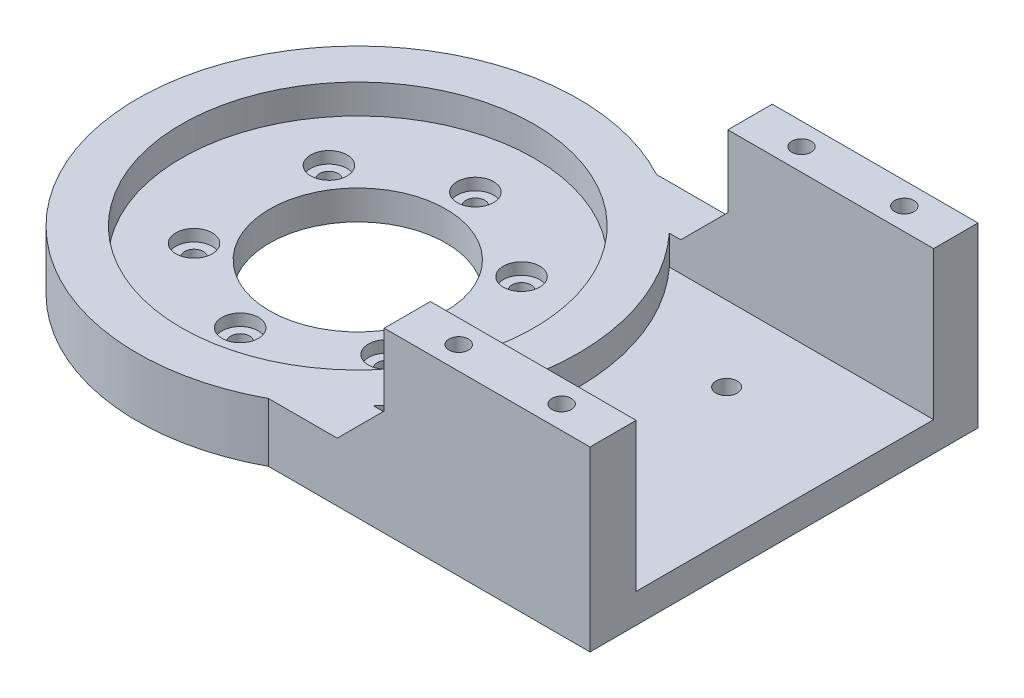
SolidWorks part; units mm, degrees
ref_plane "Front Plane" through (0, 0, 0) normal (0, 0, 1) x (1, 0, 0)
ref_plane "Top Plane" through (0, 0, 0) normal (0, 1, 0) x (1, 0, 0)
ref_plane "Right Plane" through (0, 0, 0) normal (1, 0, 0) x (0, 0, -1)
sketch "Sketch1" plane through (0, 0, 0) normal (0, 1, 0) x (1, 0, 0)
  circle A0 centre (0, 0) radius 15
  circle A1 centre (0, 0) radius 37.5
  dimension "D1" = 30
  dimension "D2" = 75
extrude "Boss-Extrude2" add sketch "Sketch1" along normal blind 5
sketch "Sketch3" plane through (0, 5, 0) normal (0, 1, 0) x (1, 0, 0)
  circle A0 centre (0, 0) radius 30
  circle A1 centre (0, 0) radius 37.5
  dimension "D1" = 60
extrude "Boss-Extrude3" add sketch "Sketch3" along normal blind 5
sketch "Sketch4" plane through (0, 5, 0) normal (0, 1, 0) x (1, 0, 0)
  line L0 (0, 0) -> (0, 20) construction
  line L1 (0, 0) -> (-16.383, 11.4715) construction
  line L2 (0, 0) -> (16.383, 11.4715) construction
  line L3 (0, 0) -> (-7.7431, 0) construction
  circle A0 centre (0, 20) radius 1.6
  circle A1 centre (-16.383, 11.4715) radius 1.6
  circle A2 centre (16.383, 11.4715) radius 1.6
  circle A3 centre (16.383, -11.4715) radius 1.6
  circle A4 centre (0, -20) radius 1.6
  circle A5 centre (-16.383, -11.4715) radius 1.6
  dimension "D2" = 3.2
  dimension "D1" = 20
  dimension "D3" = 55
  dimension "D4" = 20
  dimension "D5" = 55
  dimension "D6" = 20
extrude "Cut-Extrude1" cut sketch "Sketch4" against normal blind 5
sketch "Sketch5" plane through (0, 5, 0) normal (0, 1, 0) x (1, 0, 0)
  line L0 (0, 0) -> (-6.2782, 0) construction
  circle A0 centre (0, 20) radius 3.1
  circle A1 centre (-16.383, 11.4715) radius 3.1
  circle A2 centre (16.383, 11.4715) radius 3.1
  circle A3 centre (16.383, -11.4715) radius 3.1
  circle A4 centre (-16.383, -11.4715) radius 3.1
  circle A5 centre (0, -20) radius 3.1
  dimension "D1" = 6.2
extrude "Cut-Extrude2" cut sketch "Sketch5" against normal blind 2
sketch "Sketch6" plane through (0, 5, 0) normal (0, 1, 0) x (1, 0, 0)
  line L1 (-15, 0) -> (15, 0) construction
  circle A1 centre (0, 0) radius 15 construction
ref_plane "Plane1" through (37.5, 0, 0) normal (1, 0, 0) x (0, 0, -1)
sketch "Sketch8" plane through (37.5, 0, 0) normal (1, 0, 0) x (0, 0, -1)
  line L0 (0, 10) -> (0, 0) construction
  line L1 (37.5, 10) -> (-37.5, 10) construction
  line L2 (0, 5) -> (-25.15, 5) construction
  line L3 (0, 5) -> (25.45, 5) construction
  line L4 (-10.1453, 5) -> (-10.1453, 0) construction
  line L5 (-37.5, 0) -> (37.5, 0) construction
  line L6 (33, 5) -> (-33, 5) construction
  line L7 (33, 10) -> (33, 0)
  line L8 (-33, 0) -> (-33, 10)
  line L9 (30, 10) -> (-30, 10) construction
  line L10 (-33, 10) -> (-25.15, 10)
  line L11 (-25.15, 10) -> (-25.15, 5)
  line L12 (-25.15, 5) -> (25.45, 5)
  line L13 (25.45, 5) -> (25.45, 10)
  line L14 (25.45, 10) -> (33, 10)
  line L15 (-33, 0) -> (33, 0)
  dimension "D1" = 25.15
  dimension "D2" = 33
extrude "Boss-Extrude4" add sketch "Sketch8" along normal blind 35 and the other way up to surface contours L15 L7 L14 L13 L12 | L8 L15 L12 L11 L10 region at (37.5, 3.4459, 0.0932) other way up to face at (0, 0, 37.5)
sketch "Sketch9" plane through (0, 10, 0) normal (0, 1, 0) x (1, 0, 0)
  line L0 (37.5, -5.5) -> (37.5, 5.5) construction
  line L1 (37.5, -33) -> (72.5, -33)
  line L2 (37.5, -33) -> (37.5, -25.15)
  line L3 (37.5, -25.15) -> (72.5, -25.15)
  line L4 (72.5, -33) -> (72.5, -25.15)
  line L5 (72.5, -33) -> (17.8115, -33) construction
  line L6 (72.5, 25.45) -> (27.5417, 25.45) construction
  line L7 (72.5, 33) -> (37.5, 33)
  line L8 (72.5, 33) -> (72.5, 25.45)
  line L9 (72.5, 25.45) -> (37.5, 25.45)
  line L10 (37.5, 33) -> (37.5, 25.45)
extrude "Boss-Extrude5" add sketch "Sketch9" along normal blind 20.2
chamfer "Chamfer1" distance 8 angle 45 2 edges at (37.5, 10, -29.225) (37.5, 10, 29.075)
sketch "Sketch11" plane through (0, 30.2, 0) normal (0, 1, 0) x (1, 0, 0)
  line L0 (72.5, 29.225) -> (63.75, 29.225) construction
  line L1 (72.5, 25.45) -> (72.5, 33) construction
  line L2 (72.5, -29.075) -> (63.75, -29.075) construction
  line L3 (72.5, -33) -> (72.5, -25.15) construction
  line L4 (37.5, -29.075) -> (46.25, -29.075) construction
  line L5 (37.5, -5.5) -> (37.5, 5.5) construction
  line L6 (37.5, 29.225) -> (46.25, 29.225) construction
  line L7 (72.5, 33) -> (37.5, 33) construction
  circle A0 centre (46.25, 29.225) radius 1.65
  circle A1 centre (63.75, 29.225) radius 1.65
  circle A2 centre (63.75, -29.075) radius 1.65
  circle A3 centre (46.25, -29.075) radius 1.65
  dimension "D3" = 3.3
  dimension "D1" = 8.75
  dimension "D2" = 8.75
  dimension "D4" = 3.775
extrude "Cut-Extrude3" cut sketch "Sketch11" against normal through all
sketch "Sketch12" plane through (0, 0, 0) normal (0, -1, 0) x (1, 0, 0)
  circle A0 centre (46.25, 29.075) radius 3.1
  circle A1 centre (63.75, 29.075) radius 3.1
  circle A2 centre (63.75, -29.225) radius 3.1
  circle A3 centre (46.25, -29.225) radius 3.1
  dimension "D1" = 6.2
extrude "Cut-Extrude4" cut sketch "Sketch12" against normal blind 2.5
sketch "Sketch15" plane through (0, 5, 0) normal (0, 1, 0) x (1, 0, 0)
  line L1 (72.5, -25.15) -> (27.816, -25.15) construction
  line L3 (50.0898, 0) -> (37.5, 0) construction
  line L4 (37.5, -5.5) -> (37.5, 5.5) construction
  line L5 (43.7949, 0) -> (43.7949, 25.45) construction
  line L6 (37.5, 25.45) -> (72.5, 25.45) construction
  line L7 (43.7949, 0) -> (43.7949, -25.15) construction
  circle A1 centre (50.0898, 12.65) radius 1.8
  circle A2 centre (50.0898, -12.65) radius 1.8
  dimension "D1" = 3.6
extrude "Cut-Extrude5" cut sketch "Sketch15" against normal blind 10
